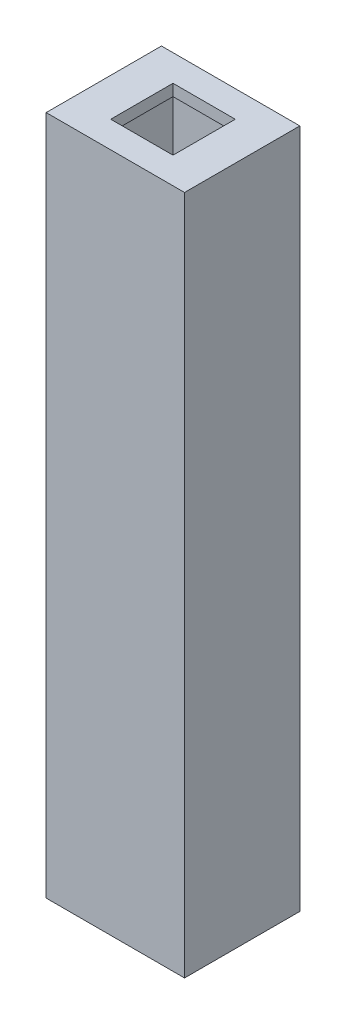
SolidWorks part; units mm, degrees
ref_plane "前视基准面" through (0, 0, 0) normal (0, 0, 1) x (1, 0, 0)
ref_plane "上视基准面" through (0, 0, 0) normal (0, 1, 0) x (1, 0, 0)
ref_plane "右视基准面" through (0, 0, 0) normal (1, 0, 0) x (0, 0, -1)
other "Configuration Table"
sketch "草图1" plane through (0, 0, 0) normal (0, 1, 0) x (1, 0, 0)
  line L1 (-3.1, 3.1) -> (3.1, 3.1)
  line L2 (-3.1, 3.1) -> (-3.1, -3.1)
  line L3 (-3.1, -3.1) -> (3.1, -3.1)
  line L4 (3.1, 3.1) -> (3.1, -3.1)
  line L5 (-3.1, 3.1) -> (3.1, -3.1) construction
  line L6 (-3.1, -3.1) -> (3.1, 3.1) construction
  line L7 (-6, 5) -> (6, 5)
  line L8 (-6, 5) -> (-6, -5)
  line L9 (-6, -5) -> (6, -5)
  line L10 (6, 5) -> (6, -5)
  line L11 (-6, 5) -> (6, -5) construction
  line L12 (-6, -5) -> (6, 5) construction
  line L13 (-2.7, -2.7) -> (2.7, -2.7)
  line L14 (-2.7, -2.7) -> (-2.7, 2.7)
  line L15 (-2.7, 2.7) -> (2.7, 2.7)
  line L16 (2.7, -2.7) -> (2.7, 2.7)
  line L17 (-2.7, -2.7) -> (2.7, 2.7) construction
  line L18 (-2.7, 2.7) -> (2.7, -2.7) construction
  point P0 (0, 0)
  point P5 (0, 0)
  point P13 (0, 0)
  dimension "D1" = 6.2
  dimension "D2" = 10
  dimension "D3" = 5.4
  dimension "D4" = 12
extrude "凸台-拉伸1" add sketch "草图1" along normal blind 54 contours L10 L7 L8 L9 L1 L4 L3 L2 region at (0, 0, -4.8438)
extrude "凸台-拉伸2" add sketch "草图1<3>" against normal blind 1 from surface contours L10 L7 L8 L9 L1 L4 L3 L2 | L4 L1 L2 L3 L16 L13 L14 L15 region at (0, 0, -3.0123) region at (0, 0, -4.8438) starting at face at (0, 54, 0)
sketch "草图1<3>" plane through (0, 0, 0) normal (0, 1, 0) x (1, 0, 0) same geometry as "草图1"
sketch "草图3" plane through (0, 0, 0) normal (0, -1, 0) x (1, 0, 0)
  line L1 (-3.6, 3.6) -> (3.6, 3.6)
  line L2 (-3.6, 3.6) -> (-3.6, -3.6)
  line L3 (-3.6, -3.6) -> (3.6, -3.6)
  line L4 (3.6, 3.6) -> (3.6, -3.6)
  line L5 (-3.6, 3.6) -> (3.6, -3.6) construction
  line L6 (-3.6, -3.6) -> (3.6, 3.6) construction
  line L7 (-6, 5) -> (6, 5)
  line L8 (-6, 5) -> (-6, -5)
  line L9 (-6, -5) -> (6, -5)
  line L10 (6, 5) -> (6, -5)
  point P0 (0, 0)
  dimension "D1" = 7.2
extrude "凸台-拉伸3" add sketch "草图3" along normal blind 5 contours L8 L9 L10 L7 | L2 L3 L4 L1
sketch "草图2" plane through (0, -5, 0) normal (0, -1, 0) x (1, 0, 0)
  line L0 (-6, -5) -> (-6, 5) construction
  line L8 (-6, 5) -> (6, 5) construction
  line L9 (-6, -5) -> (6, -5) construction
  line L10 (6, -5) -> (6, 5) construction
  circle A0 centre (-4.5, 3.5) radius 0.3
  circle A1 centre (4.5, -3.5) radius 0.3
  circle A2 centre (4.5, 3.5) radius 0.3
  circle A3 centre (-4.5, -3.5) radius 0.3
  point P0 (0, 0)
  dimension "D2" = 0.6
  dimension "D3" = 1.5
  dimension "D4" = 1.5
  dimension "D5" = 1.5
  dimension "D6" = 1.5
extrude "切除-拉伸1" cut sketch "草图2" against normal blind 2 contours A0 | A2 | A3 | A1
